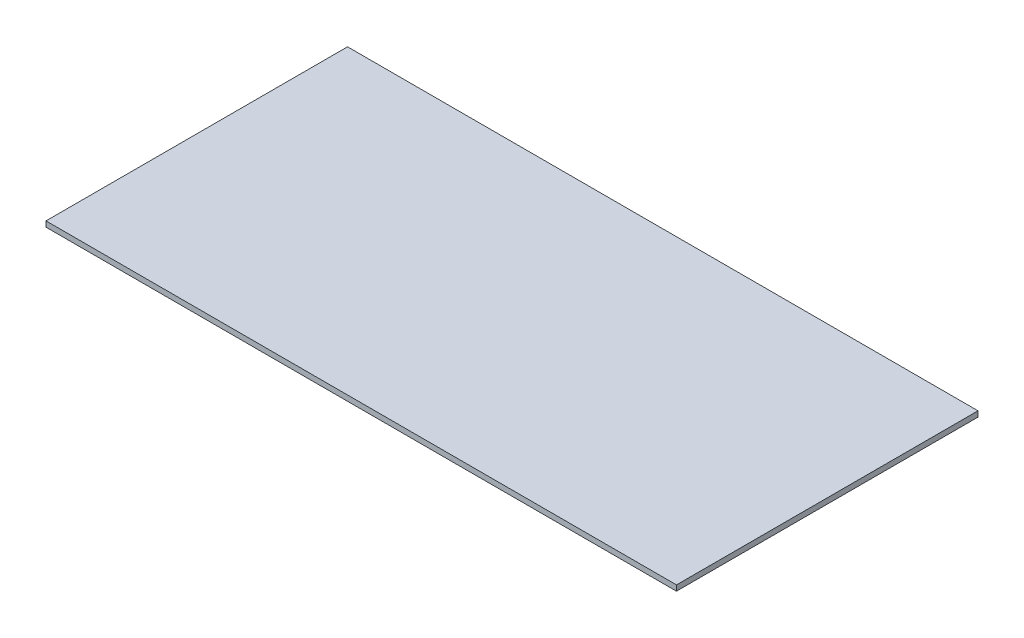
SolidWorks part; units mm, degrees
material "PC High Viscosity"
ref_plane "Front Plane" through (0, 0, 0) normal (0, 0, 1) x (1, 0, 0)
ref_plane "Top Plane" through (0, 0, 0) normal (0, 1, 0) x (1, 0, 0)
ref_plane "Right Plane" through (0, 0, 0) normal (1, 0, 0) x (0, 0, -1)
sketch "Sketch1" plane through (0, 0, 0) normal (0, 1, 0) x (1, 0, 0)
  line L1 (0, 0) -> (584.2, 0)
  line L2 (0, 0) -> (0, 279.4)
  line L3 (0, 279.4) -> (584.2, 279.4)
  line L4 (584.2, 0) -> (584.2, 279.4)
  dimension "D1" = 584.2
  dimension "D2" = 279.4
extrude "Boss-Extrude1" add sketch "Sketch1" along normal blind 5.08
sketch "Sketch2" plane through (0, 5.08, 0) normal (0, 1, 0) x (1, 0, 0)
  line L1 (50.8, 228.6) -> (228.6, 228.6)
  line L2 (50.8, 228.6) -> (50.8, 50.8)
  line L3 (50.8, 50.8) -> (228.6, 50.8)
  line L4 (228.6, 228.6) -> (228.6, 50.8)
  line L6 (584.2, 279.4) -> (0, 279.4) construction
  line L7 (0, 279.4) -> (0, 0) construction
  line L9 (254, 228.6) -> (431.8, 228.6)
  line L10 (254, 228.6) -> (254, 50.8)
  line L11 (254, 50.8) -> (431.8, 50.8)
  line L12 (431.8, 228.6) -> (431.8, 50.8)
  dimension "D1" = 177.8
  dimension "D2" = 177.8
  dimension "D3" = 50.8
  dimension "D4" = 50.8
  dimension "D5" = 177.8
  dimension "D6" = 177.8
  dimension "D7" = 25.4
  dimension "D8" = 50.8
